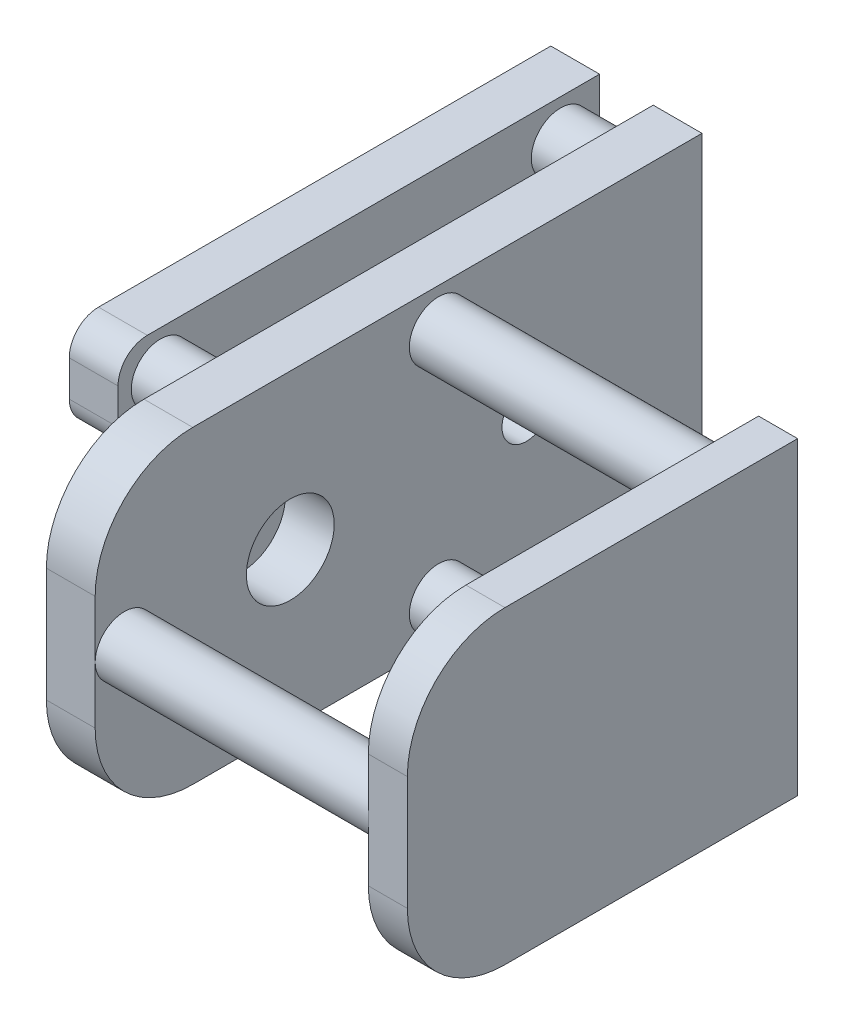
SolidWorks part; units mm, degrees
ref_plane "前视基准面" through (0, 0, 0) normal (0, 0, 1) x (1, 0, 0)
ref_plane "上视基准面" through (0, 0, 0) normal (0, 1, 0) x (1, 0, 0)
ref_plane "右视基准面" through (0, 0, 0) normal (1, 0, 0) x (0, 0, -1)
sketch "草图1" plane through (0, 0, 0) normal (1, 0, 0) x (0, 0, -1)
  line L1 (31.1, -15.85) -> (-21.1, -15.85)
  line L2 (31.1, -15.85) -> (31.1, 15.85)
  line L3 (31.1, 15.85) -> (-21.1, 15.85)
  line L4 (-31.1, -5.85) -> (-31.1, 5.85)
  line L5 (31.1, -15.85) -> (-31.1, 15.85) construction
  line L6 (31.1, 15.85) -> (-31.1, -15.85) construction
  circle A0 centre (-11.1, 0) radius 4.5
  circle A1 centre (13.1, 0) radius 2.5
  arc A2 (-31.1, -5.85) -> (-21.1, -15.85) centre (-21.1, -5.85) ccw
  arc A3 (-21.1, 15.85) -> (-31.1, 5.85) centre (-21.1, 5.85) ccw
  point P0 (0, 0)
  dimension "D3" = 9
  dimension "D6" = 5
  dimension "D7" = 10
  dimension "D1" = 31.7
  dimension "D2" = 62.2
  dimension "D4" = 20
  dimension "D5" = 18
extrude "凸台-拉伸1" add sketch "草图1" along normal blind 5
sketch "草图2" plane through (5, 0, 0) normal (1, 0, 0) x (0, 0, -1)
  line L0 (-31.1, 5.85) -> (-31.1, -5.85) construction
  line L1 (31.1, 15.85) -> (-21.1, 15.85) construction
  line L2 (-21.1, -15.85) -> (31.1, -15.85) construction
  line L3 (31.1, -15.85) -> (31.1, 15.85) construction
  circle A0 centre (-28.1, 0) radius 3
  circle A1 centre (4.1, 11.85) radius 3
  circle A2 centre (4.1, -11.85) radius 3
  dimension "D1" = 6
  dimension "D2" = 6
  dimension "D3" = 6
  dimension "D4" = 3
  dimension "D5" = 4
  dimension "D6" = 4
  dimension "D7" = 27
  dimension "D8" = 27
extrude "凸台-拉伸2" add sketch "草图2" along normal blind 28
sketch "草图3" plane through (33, 0, 0) normal (1, 0, 0) x (0, 0, -1)
  line L0 (31.1, 15.85) -> (-21.1, 15.85) construction
  line L1 (-21.1, -15.85) -> (31.1, -15.85) construction
  line L2 (-31.1, 0) -> (-31.1, -5.85) construction
  line L3 (-31.1, 5.85) -> (-31.1, 0) construction
  line L4 (8.9, 15.85) -> (-21.1, 15.85)
  line L5 (-21.1, -15.85) -> (8.9, -15.85)
  line L6 (-31.1, 0) -> (-31.1, -5.85)
  line L7 (-31.1, 5.85) -> (-31.1, 0)
  line L8 (8.9, 15.85) -> (8.9, -15.85)
  arc A0 (-31.1, -5.85) -> (-21.1, -15.85) centre (-21.1, -5.85) ccw construction
  arc A1 (-21.1, 15.85) -> (-31.1, 5.85) centre (-21.1, 5.85) ccw construction
  arc A2 (-31.1, -5.85) -> (-21.1, -15.85) centre (-21.1, -5.85) ccw
  arc A3 (-21.1, 15.85) -> (-31.1, 5.85) centre (-21.1, 5.85) ccw
  dimension "D1" = 40
extrude "凸台-拉伸3" add sketch "草图3" along normal blind 4
sketch "草图5" plane through (0, 0, 0) normal (-1, 0, 0) x (0, 0, 1)
  line L0 (-31.1, -15.85) -> (-31.1, 15.85) construction
  line L1 (-31.1, 15.85) -> (21.1, 15.85) construction
  circle A0 centre (-27.1, 11.85) radius 3
  circle A1 centre (-27.1, -11.9781) radius 3
  circle A2 centre (13.9, 11.85) radius 3
  circle A3 centre (13.9, -11.9781) radius 3
  dimension "D1" = 4
  dimension "D3" = 45
  dimension "D2" = 4
  dimension "D4" = 45
extrude "凸台-拉伸4" add sketch "草图5" along normal blind 5.5
sketch "草图6" plane through (-5.5, 0, 0) normal (-1, 0, 0) x (0, 0, 1)
  line L0 (21.1, -15.85) -> (-31.1, -15.85) construction
  line L1 (-31.1, -15.85) -> (-31.1, 15.85) construction
  line L2 (-31.1, 15.85) -> (21.1, 15.85) construction
  line L3 (15.2557, -15.85) -> (-31.1, -15.85)
  line L4 (-31.1, -15.85) -> (-31.1, 15.85)
  line L5 (-31.1, 15.85) -> (15.2557, 15.85)
  line L6 (18.2557, 12.85) -> (18.2557, 9.1837)
  line L7 (15.2557, 6.1837) -> (8.6961, 6.1837)
  line L8 (5.6961, 3.1837) -> (5.6961, -3.1837)
  line L9 (8.6961, -6.1837) -> (15.2557, -6.1837)
  line L10 (18.2557, -9.1837) -> (18.2557, -12.85)
  arc A0 (15.2557, -15.85) -> (18.2557, -12.85) centre (15.2557, -12.85) ccw
  arc A3 (18.2557, 12.85) -> (15.2557, 15.85) centre (15.2557, 12.85) ccw
  arc A4 (18.2557, -9.1837) -> (15.2557, -6.1837) centre (15.2557, -9.1837) ccw
  arc A5 (8.6961, -6.1837) -> (5.6961, -3.1837) centre (8.6961, -3.1837) cw
  arc A6 (8.6961, 6.1837) -> (5.6961, 3.1837) centre (8.6961, 3.1837) ccw
  arc A7 (18.2557, 9.1837) -> (15.2557, 6.1837) centre (15.2557, 9.1837) cw
  dimension "D2" = 3
extrude "凸台-拉伸6" add sketch "草图6" along normal blind 5
sketch "草图7" plane through (0, -15.85, 0) normal (0, -1, 0) x (1, 0, 0)
  line L3 (5, -31.1) -> (0, -31.1) construction
  circle A0 centre (2.5, 10.7) radius 1.6
  circle A1 centre (2.5, -23.1) radius 1.6
  point P6 (-2.5413, -24.7398)
  point P13 (0, 0)
  dimension "D1" = 3.2
  dimension "D2" = 3.2
  dimension "D3" = 33.8
  dimension "D4" = 8
extrude "凸台-拉伸7" add sketch "草图7" along normal blind 1
